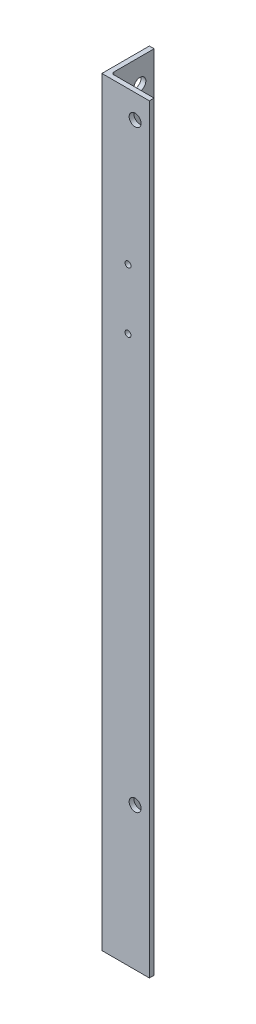
SolidWorks part; units mm, degrees
ref_plane "Front Plane" through (0, 0, 0) normal (0, 0, 1) x (1, 0, 0)
ref_plane "Top Plane" through (0, 0, 0) normal (0, 1, 0) x (1, 0, 0)
ref_plane "Right Plane" through (0, 0, 0) normal (1, 0, 0) x (0, 0, -1)
sketch "Sketch2" plane through (0, 0, 0) normal (0, 1, 0) x (1, 0, 0)
  line L0 (0, 31.75) -> (3.175, 31.75)
  line L1 (3.175, 31.75) -> (3.175, 4.7625)
  line L2 (4.7625, 3.175) -> (31.75, 3.175)
  line L3 (31.75, 3.175) -> (31.75, 0)
  line L4 (31.75, 0) -> (0, 0)
  line L5 (0, 0) -> (0, 31.75)
  arc A0 (3.175, 4.7625) -> (4.7625, 3.175) centre (4.7625, 4.7625) ccw
  point P9 (1.5875, 31.75)
  point P10 (31.75, 1.5875)
  dimension "D5" = 3.175
  dimension "D1" = 31.75
  dimension "D2" = 31.75
  dimension "D3" = 3.175
  dimension "D4" = 3.175
extrude "Boss-Extrude1" add sketch "Sketch2" along normal blind 508
sketch "FrontSideHoles-Sketch3" plane through (0, 0, 0) normal (0, 0, 1) x (1, 0, 0)
  line L0 (0, 0) -> (31.75, 0) construction
  line L1 (0, 508) -> (0, 0) construction
  circle A1 centre (22.225, 95.4) radius 4
  circle A4 centre (22.225, 492.125) radius 4
  circle A8 centre (17.4625, 406.1349) radius 2
  circle A9 centre (17.4625, 365.9349) radius 2
  dimension "D4" = 8
  dimension "D15" = 4
  dimension "D8" = 15.875
  dimension "D11" = 40.2
  dimension "D14" = 95.4
  dimension "D16" = 17.4625
  dimension "D9" = 406.1349
  dimension "D2" = 22.225
  dimension "D3" = 365.9349
sketch "LeftSideHoles-Sketch4" plane through (0, 0, 0) normal (-1, 0, 0) x (0, 0, 1)
  line L0 (-31.75, 508) -> (0, 508) construction
  line L1 (0, 508) -> (0, 0) construction
  line L3 (-31.75, 0) -> (0, 0) construction
  circle A1 centre (-22.225, 95.4) radius 4
  circle A4 centre (-22.225, 492.125) radius 4
  circle A9 centre (-22.225, 351.5849) radius 4
  dimension "D2" = 22.225
  dimension "D1" = 8
  dimension "D3" = 95.4
  dimension "D6" = 15.875
  dimension "D8" = 351.5849
  dimension "D4" = 492.125
extrude "FrontSideHoles-Cut-Extrude1" cut sketch "FrontSideHoles-Sketch3" against normal blind 3.175
extrude "LeftSideHoles-Cut-Extrude2" cut sketch "LeftSideHoles-Sketch4" against normal blind 3.175
equation "\"RailThickness\"= .125in'Spec"
equation "\"VSWidth\"= 1.25in'Spec"
equation "\"VSHeight\"= 1.25in'Spec"
equation "\"VSLength\"= 20.0in"
equation "\"HoleOffsetFromEdge\"= \"RailThickness\" * 2.5"
equation "\"VSBottomSideRailHoleYFromBottomOfLowerRailYSValue\"= 95.4mm"
equation "\"VSTopSideRailHoleYFromEdge\"= \"TopRailHeight\" / 2"
equation "\"D4@FrontSideHoles-Sketch3\"=\"FrameFastenerHoleDiameter\""
equation "\"D1@Boss-Extrude1\"=\"VSLength\""
equation "\"D8@FrontSideHoles-Sketch3\" = \"VSTopSideRailHoleYFromEdge\""
equation "\"D6@LeftSideHoles-Sketch4\" = \"VSTopSideRailHoleYFromEdge\""
equation "\"VSMidSideRailHoleYFromV8TopOfMidSideRailYSValue\"= 351.58487mm"
equation "\"D1@Sketch2\"=\"VSHeight\""
equation "\"D2@Sketch2\"=\"VSWidth\""
equation "\"TopRailHeight\"= 1.25in"
equation "\"20TGT2PulleyWidth\"= 8.7mm'The STL of the Pulley in the diagram is a bit larger"
equation "\"D11@FrontSideHoles-Sketch3\"=\"VSBeltTensionerHoleY2FromY1YSValue\""
equation "\"VSBeltTensionerHoleY1ToAlignWithYAxisGantryBlockUpperPulleyYSValue\"= 406.13487mm"
equation "\"V1 BottomOfLowerRail\"= \"LegHeight\""
equation "\"D8@LeftSideHoles-Sketch4\"= \"VSMidSideRailHoleYFromV8TopOfMidSideRailYSValue\""
equation "\"D14@FrontSideHoles-Sketch3\"=\"VSBottomSideRailHoleYFromBottomOfLowerRailYSValue\""
equation "\"BeltTensionerMountingHoleDiameter\"= 4.0mm"
equation "\"D15@FrontSideHoles-Sketch3\"=\"BeltTensionerMountingHoleDiameter\""
equation "\"VSBeltTensionerXMountingHoleOffsetFromSide\"= \"BeltTensionerMountingHoleOffsetFromEdge\" + \"RailThickness\""
equation "\"BeltTensionerMountingHoleOffsetFromEdge\"= \"HoleOffsetFromEdge\" + \"RailThickness\" * 2"
equation "\"D16@FrontSideHoles-Sketch3\"=\"VSBeltTensionerXMountingHoleOffsetFromSide\""
equation "\"D9@FrontSideHoles-Sketch3\"=\"VSBeltTensionerHoleY1ToAlignWithYAxisGantryBlockUpperPulleyYSValue\""
equation "\"FrameFastenerHoleDiameter\"= 8mm"
equation "\"FrameFastenerHoleOffsetFromSide\"= \"VSWidth\" / 2 + \"GapBetweenVerticalSupportsAndRails\""
equation "\"D2@FrontSideHoles-Sketch3\"=\"FrameFastenerHoleOffsetFromSide\""
equation "\"D2@LeftSideHoles-Sketch4\"=\"FrameFastenerHoleOffsetFromSide\""
equation "\"D3@LeftSideHoles-Sketch4\"=\"VSBottomSideRailHoleYFromBottomOfLowerRailYSValue\""
equation "\"D1@LeftSideHoles-Sketch4\"=\"FrameFastenerHoleDiameter\""
equation "\"VSBeltTensionerHoleY2FromY1YSValue\"= 40.2mm"
equation "\"GapBetweenVerticalSupportsAndRails\"= \"RailThickness\" * 2"
